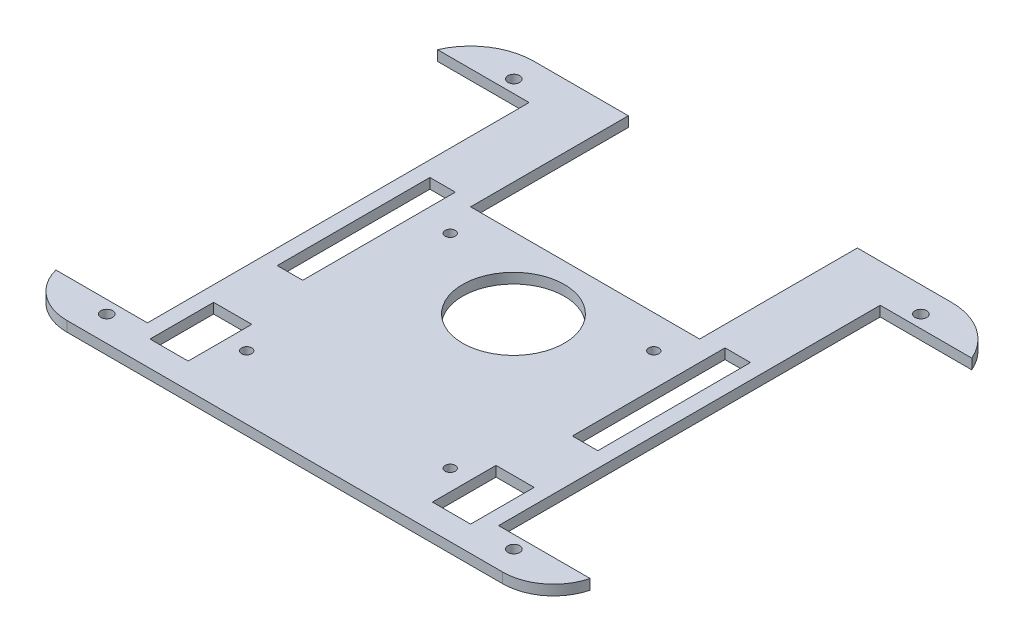
SolidWorks part; units mm, degrees
ref_plane "Front Plane" through (0, 0, 0) normal (0, 0, 1) x (1, 0, 0)
ref_plane "Top Plane" through (0, 0, 0) normal (0, 1, 0) x (1, 0, 0)
ref_plane "Right Plane" through (0, 0, 0) normal (1, 0, 0) x (0, 0, -1)
sketch "Sketch1" plane through (0, 0, 0) normal (0, 1, 0) x (1, 0, 0)
  line L0 (-150, 43.4935) -> (-114, 43.4935)
  line L2 (60, 58.4935) -> (60, 43.4935)
  line L3 (60, -121.5065) -> (-150, -121.5065)
  line L4 (-150, 58.4935) -> (-150, 43.4935)
  line L5 (-150, 58.4935) -> (-90, 58.4935)
  line L6 (-114, -31.5065) -> (-150, -31.5065) construction
  line L7 (-114, 43.4935) -> (-114, -106.5065)
  line L8 (-114, -106.5065) -> (-150, -106.5065)
  line L9 (-45, 71.907) -> (-45, -121.5065) construction
  line L10 (24, -106.5065) -> (60, -106.5065)
  line L11 (24, 43.4935) -> (24, -106.5065)
  line L12 (60, 43.4935) -> (24, 43.4935)
  line L13 (-150, -106.5065) -> (-150, -121.5065)
  line L14 (60, -106.5065) -> (60, -121.5065)
  line L15 (-90, 58.4935) -> (-90, -3.5065)
  line L16 (-90, -3.5065) -> (0, -3.5065)
  line L17 (0, -3.5065) -> (0, 58.4935)
  line L18 (0, 58.4935) -> (60, 58.4935)
  line L19 (18, -61.5065) -> (8, -61.5065)
  line L20 (-108, -1.5065) -> (-98, -1.5065)
  line L21 (-108, -1.5065) -> (-108, -61.5065)
  line L22 (-108, -61.5065) -> (-98, -61.5065)
  line L23 (-98, -1.5065) -> (-98, -61.5065)
  line L24 (-108, -1.5065) -> (-98, -61.5065) construction
  line L25 (-108, -61.5065) -> (-98, -1.5065) construction
  line L26 (8, -1.5065) -> (8, -61.5065)
  line L27 (18, -1.5065) -> (8, -1.5065)
  line L28 (18, -1.5065) -> (18, -61.5065)
  line L29 (-45, -56.5065) -> (24, -56.5065) construction
  line L30 (18, -111.5065) -> (3, -111.5065)
  line L31 (-108, -86.5065) -> (-93, -86.5065)
  line L32 (-108, -86.5065) -> (-108, -111.5065)
  line L33 (-108, -111.5065) -> (-93, -111.5065)
  line L34 (-93, -86.5065) -> (-93, -111.5065)
  line L35 (3, -86.5065) -> (3, -111.5065)
  line L36 (18, -86.5065) -> (3, -86.5065)
  line L37 (18, -86.5065) -> (18, -111.5065)
  circle A1 centre (-45.1479, -31.5065) radius 20
  circle A4 centre (-125, -111.5065) radius 2.32
  circle A5 centre (-125, 48.4935) radius 2.32
  circle A6 centre (35, 48.4935) radius 2.32
  circle A7 centre (35, -111.5065) radius 2.32
  circle A8 centre (-85, -96.5065) radius 2
  circle A9 centre (-5, -96.5065) radius 2
  circle A10 centre (-85, -16.5065) radius 2
  circle A11 centre (-5, -16.5065) radius 2
  point P0 (0, 0)
  point P2 (-103, -31.5065)
  point P20 (-150, -114.0065)
  dimension "D9" = 45
  dimension "D7" = 75
  dimension "D10" = 25
  dimension "D2" = 62
  dimension "D17" = 29
  dimension "D1" = 210
  dimension "D3" = 36
  dimension "D4" = 150
  dimension "D5" = 15
  dimension "D6" = 15
  dimension "D8" = 15
  dimension "D11" = 5
  dimension "D12" = 45
  dimension "D13" = 45
  dimension "D14" = 10
  dimension "D15" = 6
  dimension "D16" = 60
  dimension "D18" = 10
  dimension "D19" = 50
  dimension "D20" = 15
  dimension "D21" = 25
  dimension "D22" = 10
extrude "Boss-Extrude1" add sketch "Sketch1" along normal blind 4
fillet "Fillet2" radius 20 2 edges at (60, 2, 121.5065) (-150, 2, 121.5065)
fillet "Fillet3" radius 25 2 edges at (60, 2, -58.4935) (-150, 2, -58.4935)
